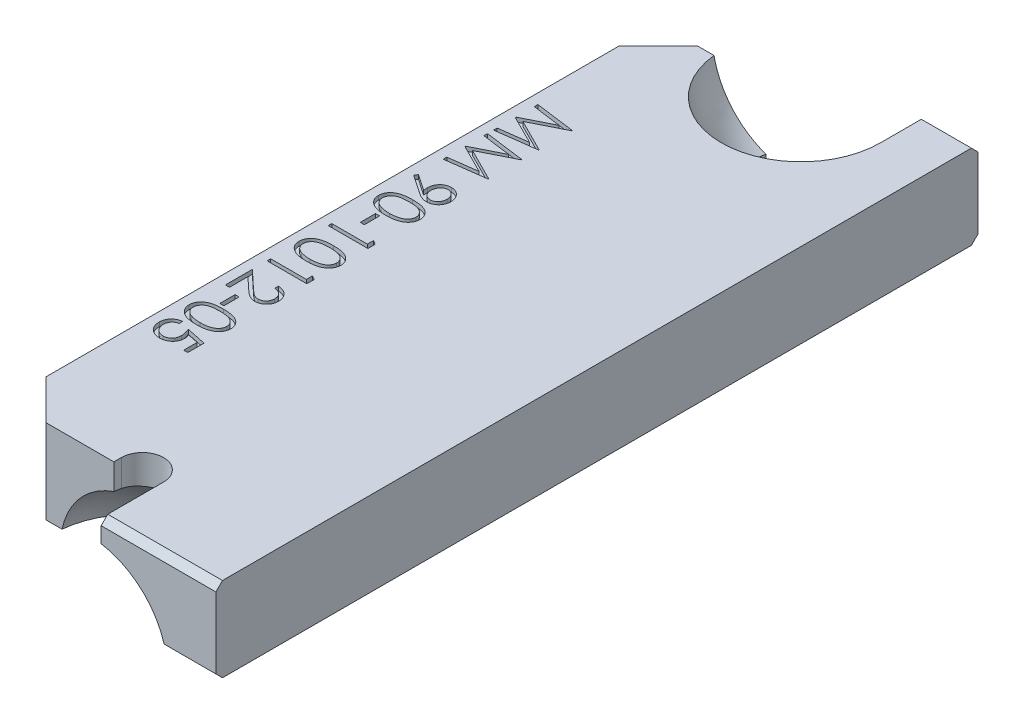
SolidWorks part; units mm, degrees
material "Acero M2"
ref_plane "Alzado" through (0, 0, 0) normal (0, 0, 1) x (1, 0, 0)
ref_plane "Planta" through (0, 0, 0) normal (0, 1, 0) x (1, 0, 0)
ref_plane "Vista lateral" through (0, 0, 0) normal (1, 0, 0) x (0, 0, -1)
sketch "Croquis1" plane through (0, 0, 0) normal (0, 1, 0) x (1, 0, 0)
  line L1 (0, 0) -> (-15.875, 0)
  line L2 (0, 0) -> (0, -45.72)
  line L3 (0, -45.72) -> (-15.875, -45.72)
  line L4 (-15.875, 0) -> (-15.875, -45.72)
  line L5 (-7.9375, -45.72) -> (-7.9375, 0) construction
  line L6 (0, -22.86) -> (-15.875, -22.86) construction
  point P180 (-7.9375, -22.86)
  dimension "D1" = 15.875
  dimension "D2" = 45.72
extrude "Saliente-Extruir1" add sketch "Croquis1" along normal blind 5.0546
sketch "Croquis2" plane through (0, 5.0546, 0) normal (0, 1, 0) x (1, 0, 0)
  line L0 (-7.7775, 0) -> (-7.7775, -2.8448) construction
  line L1 (-3.0023, 0) -> (-3.0023, -2.8448)
  line L2 (-12.5527, 0) -> (-12.5527, -2.8448)
  line L4 (-7.7775, -45.72) -> (-7.7775, -42.8752) construction
  line L5 (-12.5527, -45.72) -> (-12.5527, -42.8752) construction
  line L6 (-3.0023, -45.72) -> (-3.0023, -42.8752) construction
  line L7 (-7.7775, -2.8448) -> (-7.7775, -42.8752) construction
  line L8 (-7.7775, -22.86) -> (-15.875, -22.86) construction
  line L9 (-15.875, 0) -> (-15.875, -45.72) construction
  line L10 (-15.875, -45.72) -> (0, -45.72) construction
  line L11 (0, -45.72) -> (0, 0) construction
  arc A0 (-3.0023, 0) -> (-12.5527, 0) centre (-7.7775, 0) ccw
  arc A1 (-12.5527, -2.8448) -> (-3.0023, -2.8448) centre (-7.7775, -2.8448) ccw
  arc A2 (-12.5527, -45.72) -> (-3.0023, -45.72) centre (-7.7775, -45.72) ccw construction
  arc A3 (-3.0023, -42.8752) -> (-12.5527, -42.8752) centre (-7.7775, -42.8752) ccw construction
  point P2 (-7.7775, -1.4224)
  point P12 (-7.7775, -44.2976)
  dimension "D1" = 9.5504
  dimension "D2" = 42.8752
  dimension "D3" = 7.7775
extrude "Cortar-Extruir1" cut sketch "Croquis2" against normal offset from surface (3.8506 mm away) 1.204 up to face at (-7.9375, 0, 22.86)
sketch "Croquis6" plane through (0, 0, 0) normal (0, -1, 0) x (1, 0, 0)
  line L0 (-12.5527, 45.72) -> (-12.5527, 42.8752) construction
  line L1 (-3.0023, 45.72) -> (-3.0023, 42.8752) construction
  line L2 (-12.5527, 45.72) -> (-12.5527, 42.8752)
  line L3 (-3.0023, 45.72) -> (-3.0023, 42.8752)
  arc A0 (-12.5527, 42.8752) -> (-3.0023, 42.8752) centre (-7.7775, 42.8752) ccw construction
  arc A1 (-3.0023, 45.72) -> (-12.5527, 45.72) centre (-7.7775, 45.72) ccw construction
  arc A2 (-12.5527, 42.8752) -> (-3.0023, 42.8752) centre (-7.7775, 42.8752) ccw
  arc A3 (-3.0023, 45.72) -> (-12.5527, 45.72) centre (-7.7775, 45.72) ccw
extrude "Cortar-Extruir4" cut sketch "Croquis6" against normal offset from surface (3.7846 mm away) 1.27 up to face at (-7.8575, 5.0546, 12.7381)
fillet "Redondeo1" radius 4.7625 6 edges at (-12.5527, 1.204, 1.4224) (-3.0023, 1.204, 1.4224) (-7.7775, 1.204, 7.62) (-3.0023, 3.7846, 44.2976) (-12.5527, 3.7846, 44.2976) (-7.7775, 3.7846, 38.1)
sketch "Croquis4" plane through (0, 5.0546, 0) normal (0, 1, 0) x (1, 0, 0)
  line L0 (0, -45.72) -> (0, 0) construction
  line L1 (-15.875, 0) -> (-6.8834, 0)
  line L2 (-15.875, 0) -> (-15.875, -3.302)
  line L3 (-15.875, -3.302) -> (-6.8834, -3.302)
  line L4 (-6.8834, 0) -> (-6.8834, -3.302)
  line L5 (-11.3792, -3.302) -> (-11.3792, 0) construction
  line L6 (-15.875, -1.651) -> (-6.8834, -1.651) construction
  line L7 (-15.875, -45.72) -> (-6.8834, -45.72)
  line L8 (-15.875, -45.72) -> (-15.875, -42.418)
  line L9 (-15.875, -42.418) -> (-6.8834, -42.418)
  line L10 (-6.8834, -45.72) -> (-6.8834, -42.418)
  line L11 (-11.3792, -42.418) -> (-11.3792, -45.72) construction
  line L12 (-15.875, -44.069) -> (-6.8834, -44.069) construction
  point P68 (-11.3792, -1.651)
  point P102 (-11.3792, -44.069)
  dimension "D1" = 39.116
  dimension "D2" = 6.8834
extrude "Cortar-Extruir2" cut sketch "Croquis4" against normal through all
sketch "Croquis5" plane through (0, 5.0546, 0) normal (0, 1, 0) x (1, 0, 0)
  line L0 (-8.1534, 0) -> (-8.1534, -3.7465) construction
  line L1 (-6.8834, 0) -> (-6.8834, -3.7465)
  line L2 (-9.4234, 0) -> (-9.4234, -3.7465)
  line L3 (-8.1534, -45.72) -> (-8.1534, -41.9735) construction
  line L4 (-9.4234, -45.72) -> (-9.4234, -41.9735)
  line L5 (-6.8834, -45.72) -> (-6.8834, -41.9735)
  line L6 (-6.8834, -45.72) -> (-6.8834, -42.418) construction
  line L8 (-6.8834, -45.72) -> (0, -45.72) construction
  line L10 (-6.8834, 0) -> (-6.8834, -2.8448) construction
  line L11 (-3.0023, 0) -> (-6.8834, 0) construction
  arc A0 (-6.8834, 0) -> (-9.4234, 0) centre (-8.1534, 0) ccw
  arc A1 (-9.4234, -3.7465) -> (-6.8834, -3.7465) centre (-8.1534, -3.7465) ccw
  arc A2 (-9.4234, -45.72) -> (-6.8834, -45.72) centre (-8.1534, -45.72) ccw
  arc A3 (-6.8834, -41.9735) -> (-9.4234, -41.9735) centre (-8.1534, -41.9735) ccw
  point P2 (-8.1534, -1.8733)
  point P7 (-8.1534, -43.8468)
  dimension "D1" = 1.27
  dimension "D2" = 38.227
extrude "Cortar-Extruir3" cut sketch "Croquis5" against normal through all
chamfer "Chaflán1" distance 2.3813 angle 45 2 edges at (-15.875, 2.5273, 3.302) (-15.875, 2.5273, 42.418)
sketch "Croquis11" plane through (0, 5.0546, 0) normal (0, 1, 0) x (1, 0, 0)
  line L0 (-15.2672, -3.9098) -> (-15.2672, -41.8102) construction
  line L1 (-15.2672, -22.86) -> (-15.875, -22.86) construction
  line L2 (-15.875, -5.6833) -> (-15.875, -40.0367) construction
  text T0 "MM 90-1012-05" font "Century Gothic" height 2.3813
extrude "Cortar-Extruir9" cut sketch "Croquis11" against normal blind 0.254
chamfer "Chaflán2" distance 0.3969 angle 45 4 edges at (-1.5011, 0, 45.72) (-3.4417, 5.0546, 45.72) (-3.4417, 0, 0) (-1.5011, 5.0546, 0)
